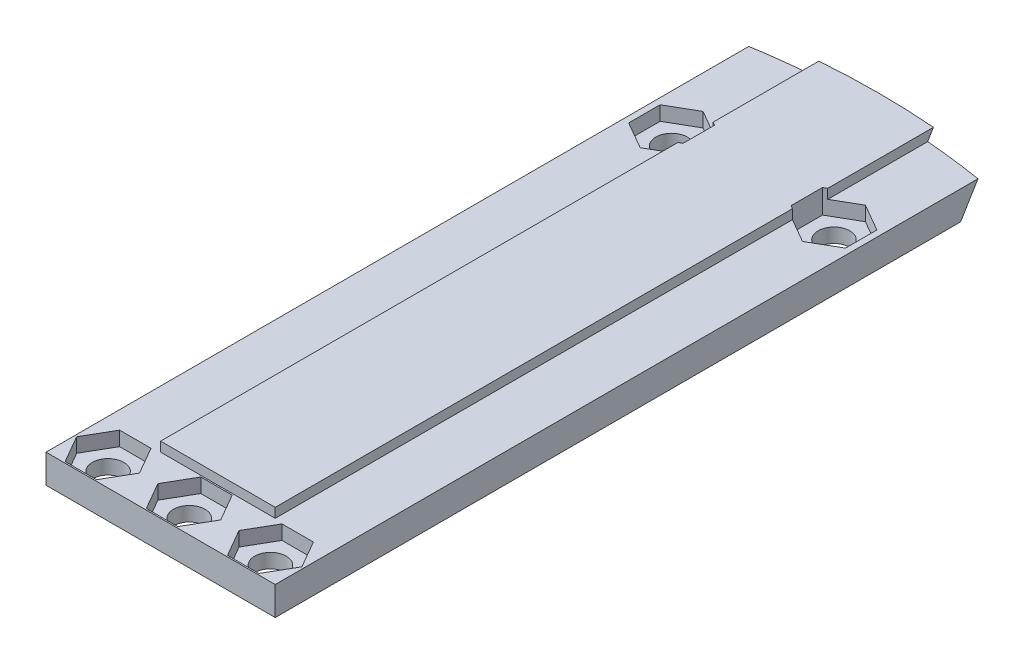
SolidWorks part; units mm, degrees
ref_plane "Front Plane" through (0, 0, 0) normal (0, 0, 1) x (1, 0, 0)
ref_plane "Top Plane" through (0, 0, 0) normal (0, 1, 0) x (1, 0, 0)
ref_plane "Right Plane" through (0, 0, 0) normal (1, 0, 0) x (0, 0, -1)
sketch "Sketch1" plane through (0, 0, 0) normal (0, 1, 0) x (1, 0, 0)
  line L1 (0, 0) -> (24, 0)
  line L2 (0, 0) -> (0, 81.5022)
  line L3 (0, 81.5022) -> (24, 81.5022)
  line L4 (24, 0) -> (24, 81.5022)
  point P4 (24, 75.3592)
  point P5 (24, 75.0833)
  dimension "D1" = 24
extrude "Boss-Extrude1" add sketch "Sketch1" along normal blind 3
sketch "Sketch2" plane through (0, 0, 0) normal (0, 1, 0) x (1, 0, 0)
  line L0 (0, 0) -> (24, 0) construction
  circle A0 centre (3.5, 3) radius 1.65
  circle A1 centre (12, 3) radius 1.65
  circle A2 centre (20.5, 3) radius 1.65
  circle A6 centre (3.5, 62) radius 1.65
  circle A8 centre (20.5, 62) radius 1.65
  circle A9 centre (12, 32.5) radius 1.65 [skipped]
  circle A10 centre (3.5, 32.5) radius 1.65 [skipped]
  circle A11 centre (20.5, 32.5) radius 1.65 [skipped]
  circle A12 centre (12, 62) radius 1.65 [skipped]
  point P9 (12, 0)
  dimension "D1" = 3.3
  dimension "D2" = 3
  dimension "D3" = 8.5
  dimension "D4" = 8.5
  dimension "D5" = 3
  dimension "D6" = 59
extrude "Cut-Extrude1" cut sketch "Sketch2" along normal through all
sketch "Sketch3" plane through (0, 0, 0) normal (0, 0, 1) x (1, 0, 0)
  line L0 (0, 3) -> (24, 3) construction
  line L1 (6, 3) -> (18, 3)
  line L2 (6, 3) -> (6, 4)
  line L3 (6, 4) -> (18, 4)
  line L4 (18, 3) -> (18, 4)
  line L5 (77.5014, 4) -> (-53.5014, 4) construction
  point P11 (12, 3)
  dimension "D1" = 12
  dimension "D2" = 12
extrude "Boss-Extrude2" add sketch "Sketch3" against normal up to surface (81.5022 mm away) from offset 6 up to face at (12, 1.5, -81.5022) offset against normal yes
ref_plane "Plane1" through (12, 0, 0) normal (-1, 0, 0) x (0, 0, 1)
sketch "Sketch4" plane through (12, 0, 0) normal (1, 0, 0) x (0, 0, -1)
  line L0 (94.4965, 36.2415) -> (19.4137, -88.8964)
  line L1 (19.4137, -88.8964) -> (139.5903, -88.8964)
  line L2 (139.5903, -88.8964) -> (139.5903, 36.2415)
  line L3 (139.5903, 36.2415) -> (94.4965, 36.2415)
  line L4 (73, -6) -> (79, 4) construction
  line L6 (0, 0) -> (0, 3) construction
  dimension "D1" = 3.3
revolve "Cut-Revolve1" cut sketch "Sketch4" angle 360 about L6
sketch "Sketch5" plane through (0, 3, 0) normal (0, 1, 0) x (1, 0, 0)
  line L0 (18, 74.3097) -> (18, 6) construction
  line L1 (15.2909, 3) -> (13.6454, 5.85)
  line L2 (13.6454, 5.85) -> (10.3546, 5.85)
  line L3 (10.3546, 5.85) -> (8.7091, 3)
  line L4 (8.7091, 3) -> (10.3546, 0.15)
  line L5 (10.3546, 0.15) -> (13.6454, 0.15)
  line L6 (13.6454, 0.15) -> (15.2909, 3)
  line L7 (23.7909, 3) -> (22.1454, 5.85)
  line L8 (22.1454, 5.85) -> (18.8546, 5.85)
  line L9 (18.8546, 5.85) -> (17.2091, 3)
  line L10 (17.2091, 3) -> (18.8546, 0.15)
  line L11 (18.8546, 0.15) -> (22.1454, 0.15)
  line L12 (22.1454, 0.15) -> (23.7909, 3)
  line L13 (6.7909, 3) -> (5.1454, 5.85)
  line L14 (5.1454, 5.85) -> (1.8546, 5.85)
  line L15 (1.8546, 5.85) -> (0.2091, 3)
  line L16 (0.2091, 3) -> (1.8546, 0.15)
  line L17 (1.8546, 0.15) -> (5.1454, 0.15)
  line L18 (5.1454, 0.15) -> (6.7909, 3)
  line L31 (6.35, 63.6454) -> (3.5, 65.2909)
  line L32 (3.5, 65.2909) -> (0.65, 63.6454)
  line L33 (0.65, 63.6454) -> (0.65, 60.3546)
  line L34 (0.65, 60.3546) -> (3.5, 58.7091)
  line L35 (3.5, 58.7091) -> (6.35, 60.3546)
  line L36 (6.35, 60.3546) -> (6.35, 63.6454)
  line L37 (23.35, 63.6454) -> (20.5, 65.2909)
  line L38 (20.5, 65.2909) -> (17.65, 63.6454)
  line L39 (17.65, 63.6454) -> (17.65, 60.3546)
  line L40 (17.65, 60.3546) -> (20.5, 58.7091)
  line L41 (20.5, 58.7091) -> (23.35, 60.3546)
  line L42 (23.35, 60.3546) -> (23.35, 63.6454)
  line L43 (6, 74.3097) -> (6, 6) construction
  circle A0 centre (12, 3) radius 2.85 construction
  circle A1 centre (20.5, 3) radius 2.85 construction
  circle A2 centre (3.5, 3) radius 2.85 construction
  circle A3 centre (3.5, 62) radius 2.85 construction
  circle A4 centre (20.5, 62) radius 2.85 construction
  dimension "D1" = 5.7
  dimension "D2" = 5.7
extrude "Cut-Extrude2" cut sketch "Sketch5" against normal blind 1.5 and the other way through all
